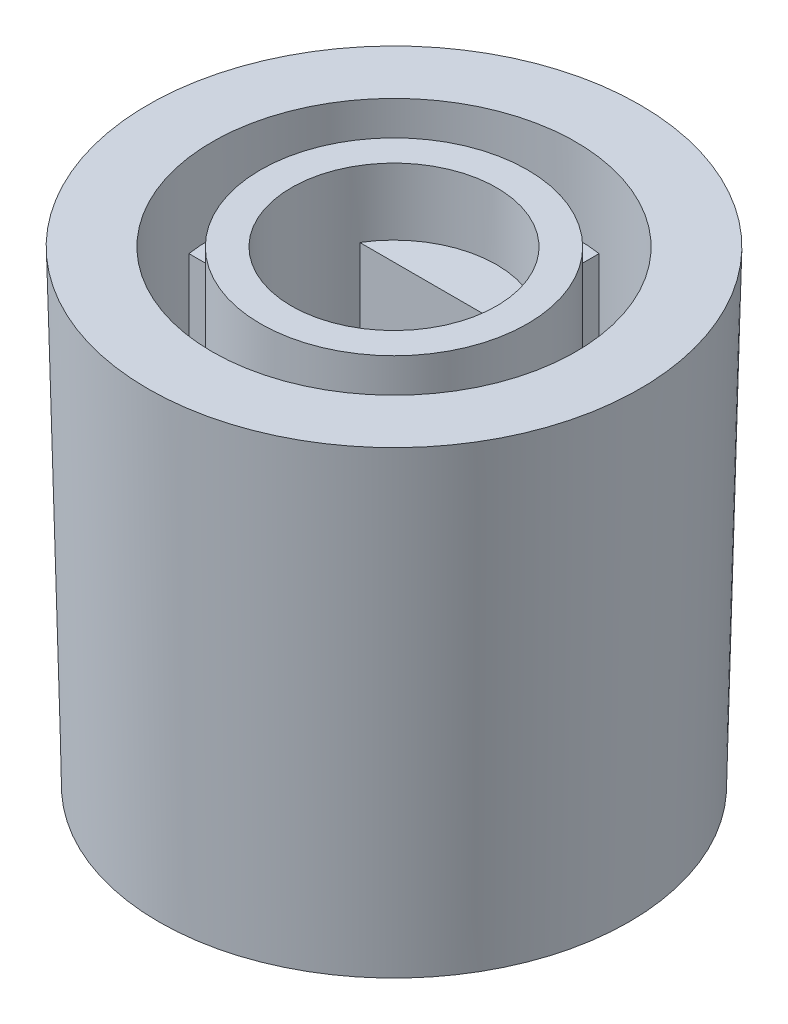
SolidWorks part; units mm, degrees
ref_plane "Front Plane" through (0, 0, 0) normal (0, 0, 1) x (1, 0, 0)
ref_plane "Top Plane" through (0, 0, 0) normal (0, 1, 0) x (1, 0, 0)
ref_plane "Right Plane" through (0, 0, 0) normal (1, 0, 0) x (0, 0, -1)
sketch "Sketch1" plane through (0, 0, 0) normal (0, 1, 0) x (1, 0, 0)
  circle A0 centre (0, 0) radius 7.05
  dimension "D1" = 14.1
extrude "Boss-Extrude1" add sketch "Sketch1" along normal blind 3.5
sketch "Sketch2" plane through (0, 3.5, 0) normal (0, 1, 0) x (1, 0, 0)
  circle A0 centre (0, 0) radius 7.05
  circle A1 centre (0, 0) radius 5.45
  circle A2 centre (0, 0) radius 7.05 construction
  dimension "D2" = 10.9
extrude "Boss-Extrude2" add sketch "Sketch2" along normal blind 10.5
draft "Draft1" type of draft neutral plane draft angle 1.325 faces to draft 1 face at (0, 0, 7.05) neutral plane through (0, 0, 0) neutral plane normal (0, -1, 0) parameters "D1"=1.325
sketch "Sketch6" plane through (0, 3.5, 0) normal (0, 1, 0) x (1, 0, 0)
  circle A0 centre (0, 0) radius 4
  dimension "D1" = 8
extrude "Boss-Extrude3" add sketch "Sketch6" along normal blind 10.5
sketch "Sketch5" plane through (0, 14, 0) normal (0, 1, 0) x (1, 0, 0)
  line L0 (-2.626, 1.6) -> (2.626, 1.6)
  circle A0 centre (0, 0) radius 3.075
  dimension "D1" = 6.15
  dimension "D2" = 1.6
extrude "Cut-Extrude1" cut sketch "Sketch5" against normal blind 9 contours L0 A0 region at (0, 14, 0.4982)
sketch "Sketch7" plane through (0, 14, 0) normal (0, 1, 0) x (1, 0, 0)
  circle A0 centre (0, 0) radius 3.075
  dimension "D1" = 6.15
extrude "Cut-Extrude2" cut sketch "Sketch7" against normal blind 2
sketch "Sketch8" plane through (0, 3.5, 0) normal (0, 1, 0) x (1, 0, 0)
  line L1 (-6.116, 0.75) -> (-3.5908, 0.75)
  line L2 (-6.116, 0.75) -> (-6.116, -0.75)
  line L3 (-6.116, -0.75) -> (-3.5908, -0.75)
  line L4 (-3.5908, 0.75) -> (-3.5908, -0.75)
  line L5 (3.6356, 0.75) -> (5.7578, 0.75)
  line L6 (3.6356, 0.75) -> (3.6356, -0.75)
  line L7 (3.6356, -0.75) -> (5.7578, -0.75)
  line L8 (5.7578, 0.75) -> (5.7578, -0.75)
  line L9 (-0.75, 3.5774) -> (0.75, 3.5774)
  line L10 (-0.75, 3.5774) -> (-0.75, 5.9145)
  line L11 (-0.75, 5.9145) -> (0.75, 5.9145)
  line L12 (0.75, 3.5774) -> (0.75, 5.9145)
  line L13 (0.75, -3.4431) -> (-0.75, -3.4431)
  line L14 (0.75, -3.4431) -> (0.75, -6.2011)
  line L15 (0.75, -6.2011) -> (-0.75, -6.2011)
  line L16 (-0.75, -3.4431) -> (-0.75, -6.2011)
  point P16 (-3.5908, 0)
  point P18 (0, 3.5774)
  dimension "D1" = 1.5
extrude "Boss-Extrude4" add sketch "Sketch8" along normal blind 8
